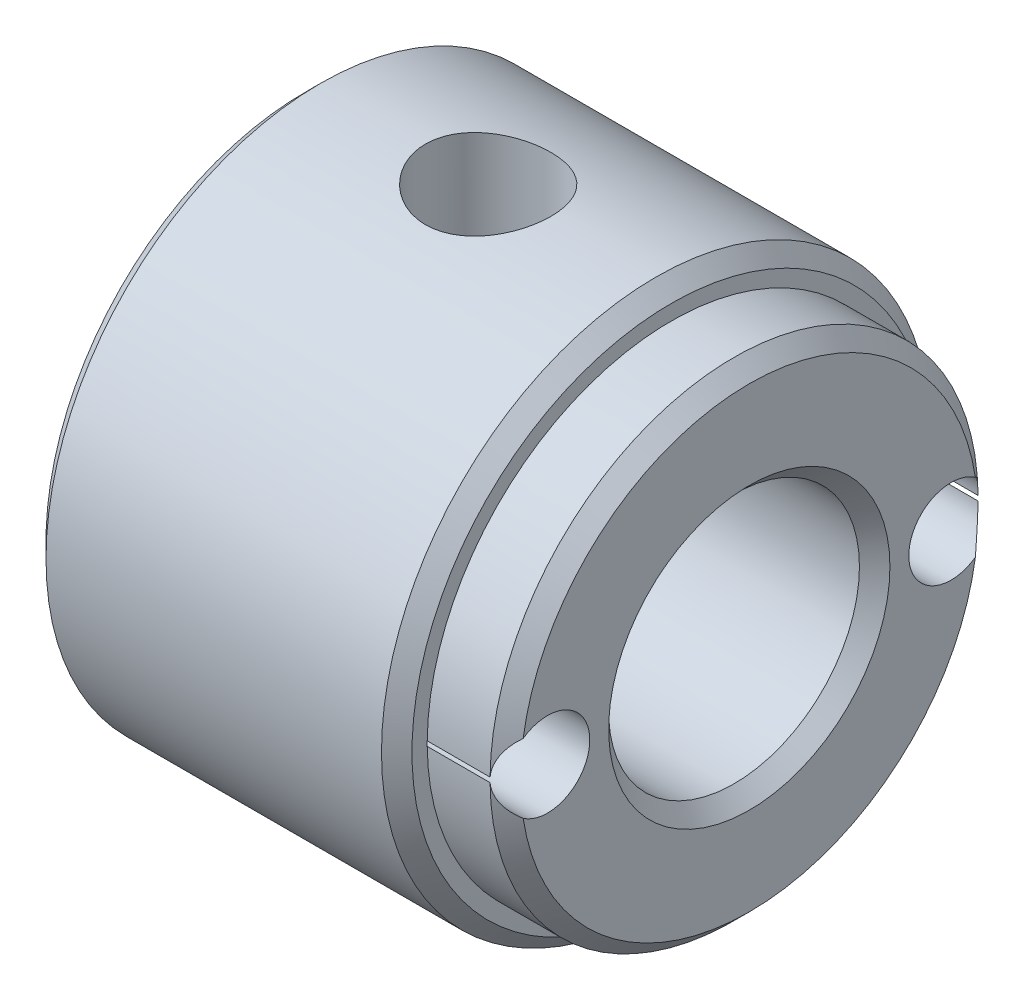
SolidWorks part; units mm, degrees
ref_plane "Front Plane" through (0, 0, 0) normal (0, 0, 1) x (1, 0, 0)
ref_plane "Top Plane" through (0, 0, 0) normal (0, 1, 0) x (1, 0, 0)
ref_plane "Right Plane" through (0, 0, 0) normal (1, 0, 0) x (0, 0, -1)
sketch "Sketch1" plane through (0, 0, 0) normal (1, 0, 0) x (0, 0, -1)
  line L0 (0, 0) -> (0, 0.7417) construction
  line L1 (-3.2639, 0) -> (-6.35, 0) construction
  circle A0 centre (0, 0) radius 6.35
  circle A1 centre (0, 0) radius 6.35
  circle A2 centre (0, 0) radius 3.2639
  circle A3 centre (-5.2515, 0) radius 1.1
  circle A5 centre (0, 0) radius 7.1438
  circle A6 centre (5.2515, 0) radius 1.1
  dimension "D1" = 12.7
  dimension "D2" = 6.5278
  dimension "D3" = 2.2
  dimension "D4" = 14.2875
  dimension "D5" = 10.5029
extrude "Inner Side Extrude" add sketch "Sketch1" along normal blind 2.032 contours A0 A2 A3 A6 region at (0, 0, -3.9718)
extrude "Outer Side Extrude" add sketch "Sketch1<3>" against normal blind 9.525 contours A0 A2 A3 A6 | A5 A0 region at (0, 0, -3.9718) region at (0, 0, 6.9417)
sketch "Sketch1<3>" plane through (0, 0, 0) normal (1, 0, 0) x (0, 0, -1) same geometry as "Sketch1"
sketch "Sketch2" plane through (0, 0, 0) normal (0, 1, 0) x (1, 0, 0)
  line L0 (-9.525, 7.1438) -> (-9.525, -7.1438) construction
  line L1 (-9.525, 0) -> (0, 0) construction
  circle A0 centre (-4.7625, 0) radius 1.632
  point P0 (-9.525, 0)
  dimension "D1" = 3.2639
  dimension "D2" = 4.7625
extrude "Clevis Pin Cut" cut sketch "Sketch2" against normal through all and the other way through all
chamfer "Chamfer so Steve Doesn't cut himself" distance 0.3969 angle 45 6 edges at (-9.525, 0, -3.2639) (2.032, 0, -3.2639) (-9.525, 0, -7.1438) (0, 0, -7.1438) (2.032, 6.35, 0) (2.032, -6.35, 0)
